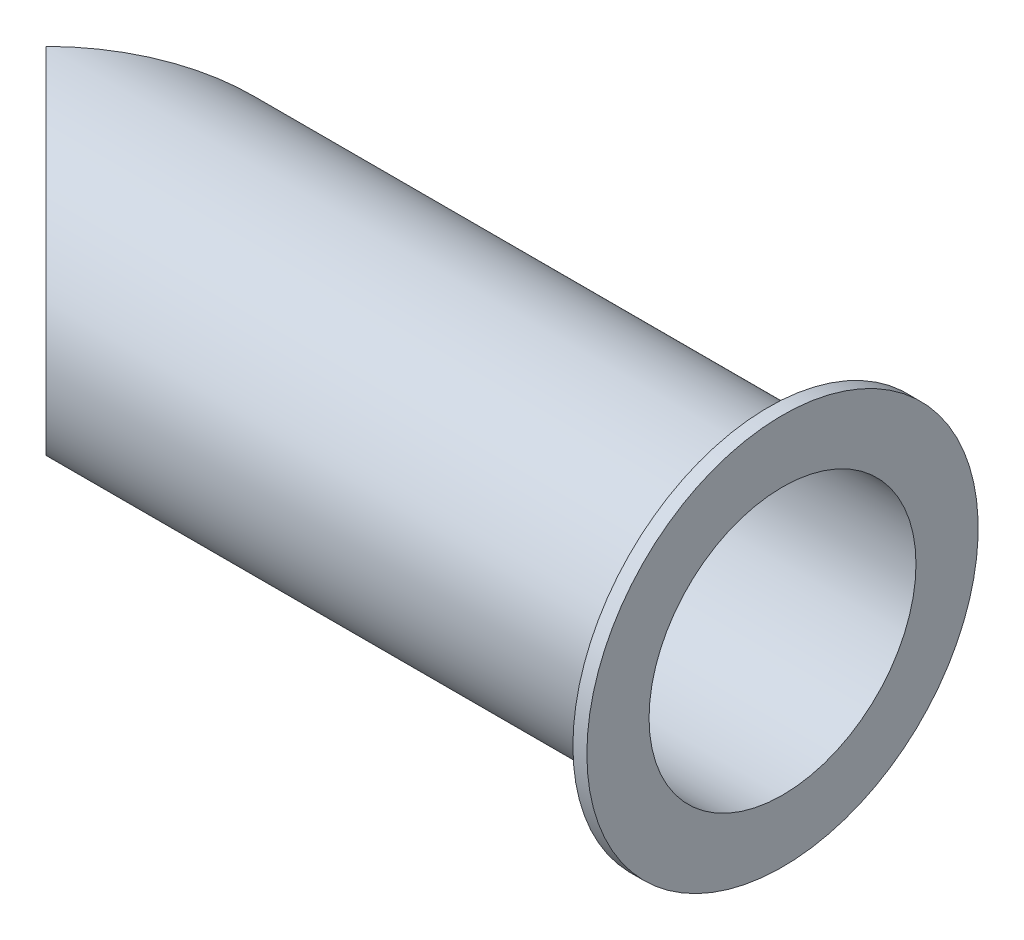
SolidWorks part; units mm, degrees
material "6061-T6 (SS)"
ref_plane "Front" through (0, 0, 0) normal (0, 0, 1) x (1, 0, 0)
ref_plane "Top" through (0, 0, 0) normal (0, 1, 0) x (1, 0, 0)
ref_plane "Right" through (0, 0, 0) normal (1, 0, 0) x (0, 0, -1)
sketch "Sketch1" plane through (0, 0, 0) normal (0, 0, 1) x (1, 0, 0)
  line L0 (0, 0) -> (0, 9.55) construction
  line L1 (0, 9.55) -> (42.2, 9.55)
  line L2 (42.2, 9.55) -> (42.2, 14)
  line L3 (42.2, 14) -> (41.2, 14)
  line L4 (41.2, 14) -> (41.2, 10.5)
  line L5 (41.2, 10.5) -> (0, 10.5)
  line L6 (0, 10.5) -> (0, 9.55)
  line L7 (0, 0) -> (42.2, 0) construction
  line L8 (0, 9.55) -> (-10.5, 9.55)
  line L9 (0, 10.5) -> (-10.5, 10.5)
  line L10 (-10.5, 10.5) -> (-10.5, 9.55)
  line L11 (-10.5, 10.5) -> (0, 10.5)
  line L12 (-10.5, -10.5) -> (-10.5, 10.5)
  arc A0 (-10.5, 10.5) -> (-10.5, -10.5) centre (-10.5, 0) cw
  point P18 (0, 0)
  dimension "D5" = 10.5
  dimension "D1" = 9.55
  dimension "D2" = 42.2
  dimension "D3" = 1
  dimension "D4" = 10.5
  dimension "D6" = 14
revolve "Revolve1" add sketch "Sketch1" angle 360 about L7 region at (22.754, 10.2037, 0) region at (-3.8508, 10.0613, 0)
extrude "Cut-Extrude1" cut sketch "Sketch1<3>" against normal through all both and the other way through all contours A0 L8 L12 | A0 L10 L8 region at (-5.9977, -0.1626, 0) region at (-8.853, 9.9315, 0)
sketch "Sketch1<3>" plane through (0, 0, 0) normal (0, 0, 1) x (1, 0, 0) same geometry as "Sketch1"
